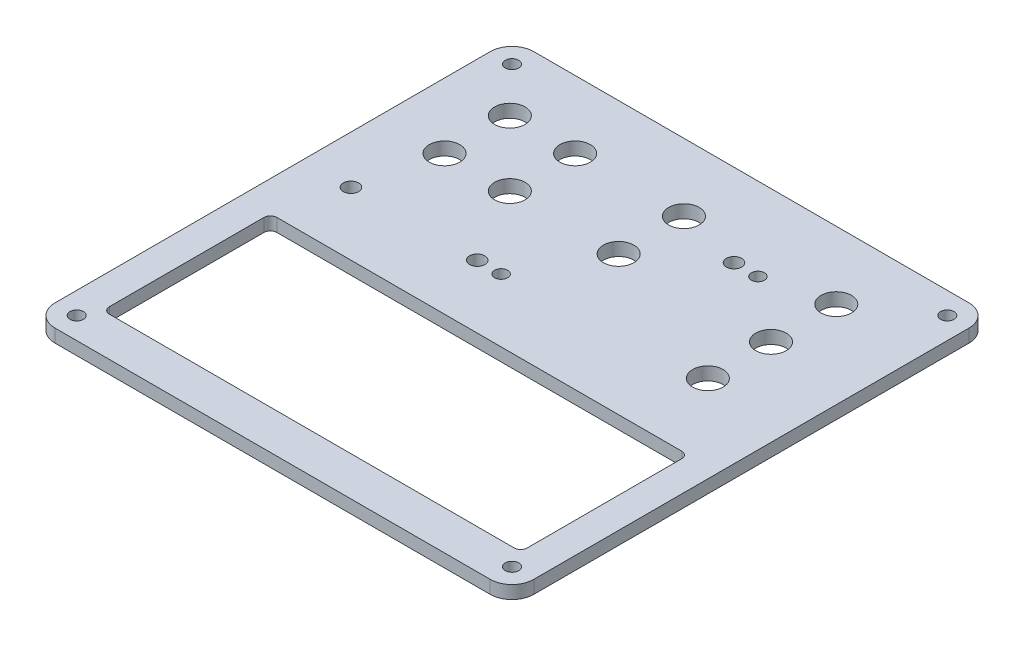
SolidWorks part; units mm, degrees
ref_plane "Front Plane" through (0, 0, 0) normal (0, 0, 1) x (1, 0, 0)
ref_plane "Top Plane" through (0, 0, 0) normal (0, 1, 0) x (1, 0, 0)
ref_plane "Right Plane" through (0, 0, 0) normal (1, 0, 0) x (0, 0, -1)
sketch "Sketch1" plane through (0, 0, 0) normal (0, 1, 0) x (1, 0, 0)
  line L1 (-55, 55) -> (55, 55)
  line L2 (-55, 55) -> (-55, -55)
  line L3 (-55, -55) -> (55, -55)
  line L4 (55, 55) -> (55, -55)
  line L5 (-55, 55) -> (55, -55) construction
  line L6 (-55, -55) -> (55, 55) construction
  circle A0 centre (-50, 50) radius 1.55
  circle A1 centre (50, 50) radius 1.55
  circle A2 centre (50, -50) radius 1.55
  circle A3 centre (-50, -50) radius 1.55
  point P0 (0, 0)
  dimension "D4" = 3.1
  dimension "D8" = 3.1
  dimension "D9" = 3.1
  dimension "D10" = 3.1
  dimension "D1" = 110
  dimension "D2" = 110
  dimension "D3" = 5
  dimension "D5" = 5
  dimension "D6" = 5
  dimension "D7" = 5
extrude "Boss-Extrude1" add sketch "Sketch1" along normal blind 3 contours A3 | A2 | A1 | A0 | L1 L4 L3 L2
fillet "Fillet1" radius 5 4 edges at (-55, 1.5, -55) (55, 1.5, -55) (55, 1.5, 55) (-55, 1.5, 55)
sketch "Sketch2" plane through (0, 3, 0) normal (0, 1, 0) x (1, 0, 0)
  line L0 (0, 55) -> (0, -55) construction
  line L1 (-48, -46) -> (48, -46)
  line L2 (-48, -46) -> (-48, -7.5)
  line L3 (-48, -7.5) -> (48, -7.5)
  line L4 (48, -46) -> (48, -7.5)
  line L5 (-50, 55) -> (50, 55) construction
  line L6 (-50, -55) -> (50, -55) construction
  line L7 (-55, 50) -> (-55, -50) construction
  line L8 (55, 50) -> (55, -50) construction
  dimension "D1" = 7
  dimension "D2" = 7
  dimension "D3" = 38.5
  dimension "D4" = 9
extrude "Cut-Extrude1" cut sketch "Sketch2" against normal through all contours L3 L4 L1 L2
fillet "Fillet2" radius 1.5 4 edges at (-48, 1.5, 46) (48, 1.5, 46) (48, 1.5, 7.5) (-48, 1.5, 7.5)
sketch "Sketch3" plane through (0, 3, 0) normal (0, 1, 0) x (1, 0, 0)
  line L0 (35, 55) -> (35, -55) construction
  line L1 (-55, 50) -> (-55, -50) construction
  line L2 (-55, 39.5) -> (55, 39.5) construction
  line L3 (55, 50) -> (55, -50) construction
  line L4 (-55, 24.5) -> (55, 24.5) construction
  line L5 (-55, 9.5) -> (55, 9.5) construction
  line L6 (-40, 55) -> (-40, -55) construction
  line L7 (-50, 55) -> (50, 55) construction
  line L8 (-50, -55) -> (50, -55) construction
  line L9 (-25, 55) -> (-25, -55) construction
  line L10 (0, 55) -> (0, -55) construction
  circle A0 centre (-40, 39.5) radius 3.5
  circle A1 centre (-40, 24.5) radius 3.5
  circle A3 centre (-25, 39.5) radius 3.5
  circle A4 centre (-25, 24.5) radius 3.5
  circle A5 centre (0, 39.5) radius 3.5
  circle A6 centre (0, 24.5) radius 3.5
  circle A7 centre (35, 39.5) radius 3.5
  circle A8 centre (35, 24.5) radius 3.5
  circle A9 centre (35, 10) radius 3.5
  dimension "D3" = 7
  dimension "D4" = 7
  dimension "D5" = 7
  dimension "D8" = 7
  dimension "D9" = 15
  dimension "D11" = 7
  dimension "D12" = 7
  dimension "D13" = 7
  dimension "D15" = 7
  dimension "D16" = 7
  dimension "D1" = 15
  dimension "D2" = 15.5
  dimension "D6" = 15
  dimension "D7" = 15
  dimension "D10" = 25
  dimension "D14" = 35
extrude "Cut-Extrude2" cut sketch "Sketch3" against normal through all contours A1 | A3 | A4 | A5 | A6 | A0 | A7 | A8 | A9 region at (-40, 3, -24.5) region at (-25, 3, -39.5) region at (-25, 3, -24.5) region at (0, 3, -39.5) region at (0, 3, -24.5)
sketch "Sketch4" plane through (0, 3, 0) normal (0, 1, 0) x (1, 0, 0)
  line L1 (-55, 50) -> (-55, -50) construction
  line L2 (55, 50) -> (55, -50) construction
  line L3 (-44, -55) -> (-44, 55) construction
  line L4 (-50, -55) -> (50, -55) construction
  line L5 (-50, 55) -> (50, 55) construction
  line L6 (-15, 55) -> (-15, -55) construction
  line L7 (-55, 7) -> (55, 7) construction
  line L8 (-55, 36) -> (55, 36) construction
  line L9 (15, 55) -> (15, -55) construction
  circle A0 centre (-44, 7) radius 1.75
  circle A1 centre (-15, 7) radius 1.75
  circle A2 centre (-9.5, 7) radius 1.5
  circle A3 centre (15, 36) radius 1.75
  circle A4 centre (20.5, 36) radius 1.5
  dimension "D3" = 3.5
  dimension "D4" = 40
  dimension "D6" = 3.5
  dimension "D8" = 3
  dimension "D9" = 3.5
  dimension "D10" = 3
  dimension "D1" = 11
  dimension "D5" = 62
  dimension "D7" = 5.5
  dimension "D11" = 5.5
  dimension "D12" = 40
  dimension "D13" = 19
extrude "Cut-Extrude3" cut sketch "Sketch4" against normal through all contours A0 | A1 | A2 | A3 | A4
